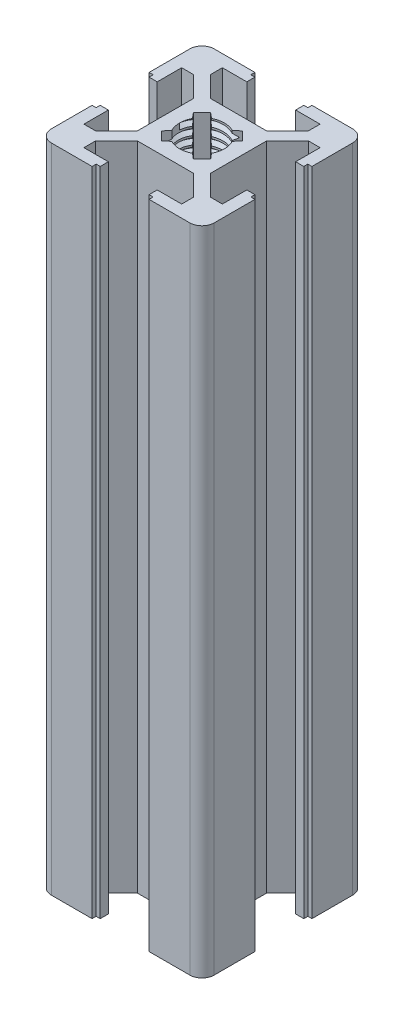
SolidWorks part; units mm, degrees
material "3.3547 (EN-AW 5083)"
ref_plane "Płaszczyzna przednia" through (0, 0, 0) normal (0, 0, 1) x (1, 0, 0)
ref_plane "Płaszczyzna górna" through (0, 0, 0) normal (0, 1, 0) x (1, 0, 0)
ref_plane "Płaszczyzna prawa" through (0, 0, 0) normal (1, 0, 0) x (0, 0, -1)
sketch "Szkic1" plane through (0, 0, 0) normal (0, 1, 0) x (1, 0, 0)
  line L0 (0, 10) -> (0, -10) construction
  line L1 (4.5, -4.5) -> (-4.5, -4.5)
  line L2 (4.5, -4.5) -> (4.5, 4.5)
  line L3 (4.5, 4.5) -> (-4.5, 4.5)
  line L4 (-4.5, -4.5) -> (-4.5, 4.5)
  line L5 (4.5, -4.5) -> (-4.5, 4.5) construction
  line L6 (4.5, 4.5) -> (-4.5, -4.5) construction
  line L7 (8.5, -10) -> (-8.5, -10)
  line L8 (10, -8.5) -> (10, 8.5)
  line L9 (8.5, 10) -> (-8.5, 10)
  line L10 (-10, -8.5) -> (-10, 8.5)
  line L11 (10, -10) -> (-10, 10) construction
  line L12 (10, 10) -> (-10, -10) construction
  line L13 (3.5, 10) -> (-3.5, 10)
  line L14 (-3.5, 10) -> (-3.5, 9.5)
  line L15 (-3.5, 9.5) -> (-3, 9.5)
  line L16 (-3, 9.5) -> (-3, 8.5)
  line L17 (-3, 8.5) -> (-6, 8.5)
  line L18 (-6, 8.5) -> (-6, 7.06)
  line L19 (-6, 7.06) -> (-3.4405, 4.5)
  line L20 (-1.9445, 3.0052) -> (-3.0052, 1.9445)
  line L21 (-1.9445, 3.0052) -> (-1.2713, 2.4385)
  line L22 (-3.0052, 1.9445) -> (-2.4385, 1.2713)
  line L23 (3.5, 10) -> (3.5, 9.5)
  line L24 (3.5, 9.5) -> (3, 9.5)
  line L25 (3, 9.5) -> (3, 8.5)
  line L26 (3, 8.5) -> (6, 8.5)
  line L27 (6, 8.5) -> (6, 7.06)
  line L28 (6, 7.06) -> (3.4405, 4.5)
  line L29 (1.9445, 3.0052) -> (3.0052, 1.9445)
  line L30 (1.9445, 3.0052) -> (1.2713, 2.4385)
  line L31 (3.0052, 1.9445) -> (2.4385, 1.2713)
  line L32 (1.9445, 3.0052) -> (1.2713, 2.4385)
  line L33 (3.0052, 1.9445) -> (1.9445, 3.0052)
  line L34 (3.0052, 1.9445) -> (2.4385, 1.2713)
  line L35 (7.06, 6) -> (4.5, 3.4405)
  line L36 (8.5, 6) -> (7.06, 6)
  line L37 (8.5, 3) -> (8.5, 6)
  line L38 (9.5, 3) -> (8.5, 3)
  line L39 (9.5, 3.5) -> (9.5, 3)
  line L40 (10, 3.5) -> (9.5, 3.5)
  line L41 (10, -3.5) -> (9.5, -3.5)
  line L42 (9.5, -3.5) -> (9.5, -3)
  line L43 (9.5, -3) -> (8.5, -3)
  line L44 (8.5, -3) -> (8.5, -6)
  line L45 (8.5, -6) -> (7.06, -6)
  line L46 (7.06, -6) -> (4.5, -3.4405)
  line L47 (3.0052, -1.9445) -> (2.4385, -1.2713)
  line L48 (3.0052, -1.9445) -> (1.9445, -3.0052)
  line L49 (1.9445, -3.0052) -> (1.2713, -2.4385)
  line L50 (3.0052, -1.9445) -> (2.4385, -1.2713)
  line L51 (1.9445, -3.0052) -> (3.0052, -1.9445)
  line L52 (1.9445, -3.0052) -> (1.2713, -2.4385)
  line L53 (6, -7.06) -> (3.4405, -4.5)
  line L54 (6, -8.5) -> (6, -7.06)
  line L55 (3, -8.5) -> (6, -8.5)
  line L56 (3, -9.5) -> (3, -8.5)
  line L57 (3.5, -9.5) -> (3, -9.5)
  line L58 (3.5, -10) -> (3.5, -9.5)
  line L59 (-3.5, -10) -> (-3.5, -9.5)
  line L60 (-3.5, -9.5) -> (-3, -9.5)
  line L61 (-3, -9.5) -> (-3, -8.5)
  line L62 (-3, -8.5) -> (-6, -8.5)
  line L63 (-6, -8.5) -> (-6, -7.06)
  line L64 (-6, -7.06) -> (-3.4405, -4.5)
  line L65 (-1.9445, -3.0052) -> (-1.2713, -2.4385)
  line L66 (-1.9445, -3.0052) -> (-3.0052, -1.9445)
  line L67 (-3.0052, -1.9445) -> (-2.4385, -1.2713)
  line L68 (-1.9445, -3.0052) -> (-1.2713, -2.4385)
  line L69 (-3.0052, -1.9445) -> (-1.9445, -3.0052)
  line L70 (-3.0052, -1.9445) -> (-2.4385, -1.2713)
  line L71 (-7.06, -6) -> (-4.5, -3.4405)
  line L72 (-8.5, -6) -> (-7.06, -6)
  line L73 (-8.5, -3) -> (-8.5, -6)
  line L74 (-9.5, -3) -> (-8.5, -3)
  line L75 (-9.5, -3.5) -> (-9.5, -3)
  line L76 (-10, -3.5) -> (-9.5, -3.5)
  line L77 (-10, 3.5) -> (-9.5, 3.5)
  line L78 (-9.5, 3.5) -> (-9.5, 3)
  line L79 (-9.5, 3) -> (-8.5, 3)
  line L80 (-8.5, 3) -> (-8.5, 6)
  line L81 (-8.5, 6) -> (-7.06, 6)
  line L82 (-7.06, 6) -> (-4.5, 3.4405)
  line L83 (-3.0052, 1.9445) -> (-2.4385, 1.2713)
  line L84 (-3.0052, 1.9445) -> (-1.9445, 3.0052)
  line L85 (-1.9445, 3.0052) -> (-1.2713, 2.4385)
  circle A0 centre (0, 0) radius 2.75
  arc A1 (10, -8.5) -> (8.5, -10) centre (8.5, -8.5) cw
  arc A2 (-10, -8.5) -> (-8.5, -10) centre (-8.5, -8.5) ccw
  arc A3 (10, 8.5) -> (8.5, 10) centre (8.5, 8.5) ccw
  arc A4 (-8.5, 10) -> (-10, 8.5) centre (-8.5, 8.5) ccw
  point P16 (0, 10)
  point P37 (-2.4749, 2.4749)
  dimension "D1" = 5.5
  dimension "D12" = 1.5
  dimension "D2" = 9
  dimension "D3" = 20
  dimension "D4" = 20
  dimension "D5" = 7
  dimension "D6" = 0.5
  dimension "D7" = 0.5
  dimension "D8" = 1
  dimension "D9" = 3
  dimension "D10" = 1.44
  dimension "D11" = 3.62
  dimension "D13" = 1.5
  dimension "D14" = 3.5
  dimension "D15" = 0.88
  dimension "D16" = 4
extrude "Dodanie-wyciągnięcie1" add sketch "Szkic1" along normal blind 80 contours L9 A4 L10 L77 L78 L79 L80 L81 L82 L4 L3 L19 L18 L17 L16 L15 L14 | L8 A3 L9 L23 L24 L25 L26 L27 L28 L3 L2 L35 L36 L37 L38 L39 L40 | L4 L1 L2 L3 A0 L47 L48 L49 L65 L66 L67 L22 L20 L21 L30 L29 L31 | L10 A2 L7 L59 L60 L61 L62 L63 L64 L1 L4 L71 L72 L73 L74 L75 L76 | A1 L8 L41 L42 L43 L44 L45 L46 L2 L1 L53 L54 L55 L56 L57 L58 L7 region at (7.2228, 0, 7.2228) region at (3.9703, 0, 4.3727) region at (-7.2228, 0, 7.2228) region at (7.2228, 0, -7.2228) region at (-7.2228, 0, -7.2228)
thread "Thread1" pitch 1 method cut profile "Thread Profile1" start angle 0, offset 0, length 20, pitch 1, diameter 5.5
ref_plane "Plane1" through (-2.75, 80, 0) normal (0, 0, 1) x (-1, 0, 0)
sketch "Thread Profile1" plane through (-2.75, 80, 0) normal (0, 0, 1) x (-1, 0, 0)
  line L0 (0, 0) -> (0, 1) construction
  line L1 (0, 0) -> (0.5413, 0.3125)
  line L2 (0.5413, 0.3125) -> (0.5413, 0.4375)
  line L3 (0.5413, 0.4375) -> (0, 0.75)
  line L4 (0.5413, 0.375) -> (0, 0.375) construction
  line L11 (0, 0) -> (0, 0.75)
  point P2 (0, 0)
  dimension "Pitch" = 1
  dimension "Profile_Angle" = 60
  dimension "Profile_Land" = 0.125
  dimension "Profile_Height" = 0.5413
thread "Thread2" pitch 1 method cut profile "Thread Profile2" start angle 0, offset 0, length 20, pitch 1, diameter 5.5
ref_plane "Plane2" through (2.75, 0, 0) normal (0, 0, 1) x (1, 0, 0)
sketch "Thread Profile2" plane through (2.75, 0, 0) normal (0, 0, 1) x (1, 0, 0)
  line L0 (0, 0) -> (0, 1) construction
  line L1 (0, 0) -> (0.5413, 0.3125)
  line L2 (0.5413, 0.3125) -> (0.5413, 0.4375)
  line L3 (0.5413, 0.4375) -> (0, 0.75)
  line L4 (0.5413, 0.375) -> (0, 0.375) construction
  line L11 (0, 0) -> (0, 0.75)
  point P2 (0, 0)
  dimension "Pitch" = 1
  dimension "Profile_Angle" = 60
  dimension "Profile_Land" = 0.125
  dimension "Profile_Height" = 0.5413
